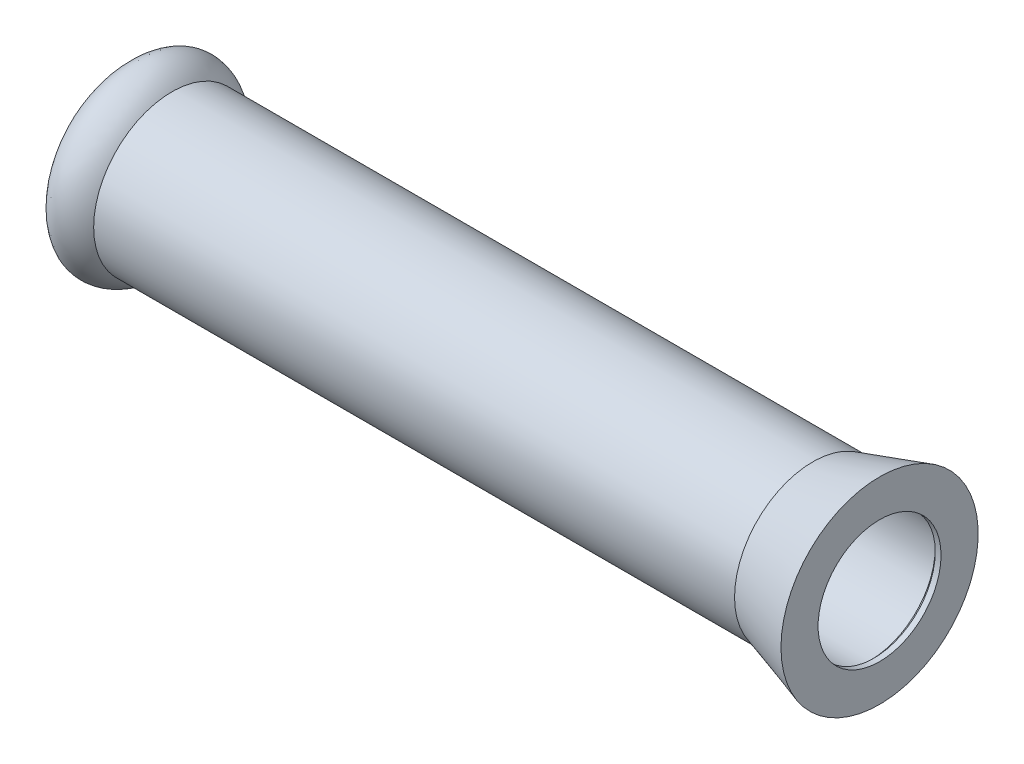
SolidWorks part; units mm, degrees
ref_plane "Front Plane" through (0, 0, 0) normal (0, 0, 1) x (1, 0, 0)
ref_plane "Top Plane" through (0, 0, 0) normal (0, 1, 0) x (1, 0, 0)
ref_plane "Right Plane" through (0, 0, 0) normal (1, 0, 0) x (0, 0, -1)
sketch "Sketch1" plane through (0, 0, 0) normal (1, 0, 0) x (0, 0, -1)
  circle A0 centre (0, 0) radius 11.2
  circle A1 centre (0, 0) radius 13.5
  dimension "D1" = 22.4
  dimension "D2" = 27
extrude "Boss-Extrude1" add sketch "Sketch1" along normal blind 60
sketch "Sketch2" plane through (0, 0, 0) normal (0, 0, 1) x (1, 0, 0)
  line L0 (8, 12.6) -> (8, 9.6)
  line L1 (8, 9.6) -> (11, 9.6)
  line L2 (0, 13.5) -> (0, -13.5) construction
  arc A0 (8, 12.6) -> (11, 9.6) centre (8, 9.6) cw
  dimension "D1" = 3
  dimension "D2" = 12.6
  dimension "D3" = 8
revolve "Cut-Revolve1" cut sketch "Sketch2" angle 360 about L0
pattern_circular "CirPattern1" count 8 over 360 about axis through (60, 0, 0) along (-1, 0, 0) of "Cut-Revolve1" reverse direction yes
pattern_linear "LPattern1" count 3 spacing 20 along (1, 0, 0) of "CirPattern1"
fillet "Fillet1" radius 3 1 edges at (0, 0, -11.2)
sketch "Sketch3" plane through (0, 0, 0) normal (0, 0, 1) x (1, 0, 0)
  line L0 (0, 0) -> (130, 0) construction
  line L1 (60, 13.5) -> (0, 13.5) construction
  line L2 (8, 13.5) -> (118.5, 13.5)
  line L3 (118.5, 13.5) -> (130, 17)
  line L4 (130, 17) -> (130, 11.2)
  line L5 (130, 11.2) -> (60, 11.2)
  line L7 (16.1283, 3.813) -> (-0.3646, 23.4685) construction
  line L9 (60, 11.2) -> (60, 13)
  line L10 (60, -13.5) -> (60, 13.5) construction
  line L12 (60, -11.2) -> (60, 11.2) construction
  line L13 (0, 13.5) -> (0, -13.5) construction
  line L14 (0, 13.5) -> (0, 13)
  line L15 (0, 13) -> (60, 13)
  line L16 (6.095, 22.2046) -> (-6.095, 4.7954) construction
  line L17 (10.0605, 18.479) -> (-4.9197, 13.0267) construction
  spline S0 degree 3 poles (0, 13.5) (0.6883, 14.483) (1.6099, 15.4403) (4.1318, 16.2823) (6.4573, 15.3385) (8, 13.5) knots 0 0 0 0 0.338781 0.438781 1 1 1 1
  point P17 (60, 11.2)
  dimension "D6" = 4
  dimension "D8" = 20
  dimension "D9" = 8
  dimension "D10" = 8
  dimension "D1" = 130
  dimension "D2" = 13.5
  dimension "D3" = 15.7272
  dimension "D4" = 11.5
  dimension "D5" = 3.5
  dimension "D7" = 55
  dimension "D11" = 50
  dimension "D12" = 8
  dimension "D13" = 2.5
  dimension "D14" = 0.5
revolve "Revolve1" add sketch "Sketch3" angle 360 about L0
sketch "Sketch4" plane through (130, 0, 0) normal (1, 0, 0) x (0, 0, -1)
  circle A0 centre (0, 0) radius 11.2 construction
  circle A1 centre (0, 0) radius 11.2
  circle A2 centre (0, 0) radius 10.6
  dimension "D1" = 0.6
extrude "Boss-Extrude2" add sketch "Sketch4" against normal blind 1
chamfer "Chamfer1" distance 0.6 angle 45 1 edges at (129, 0, -11.2)
